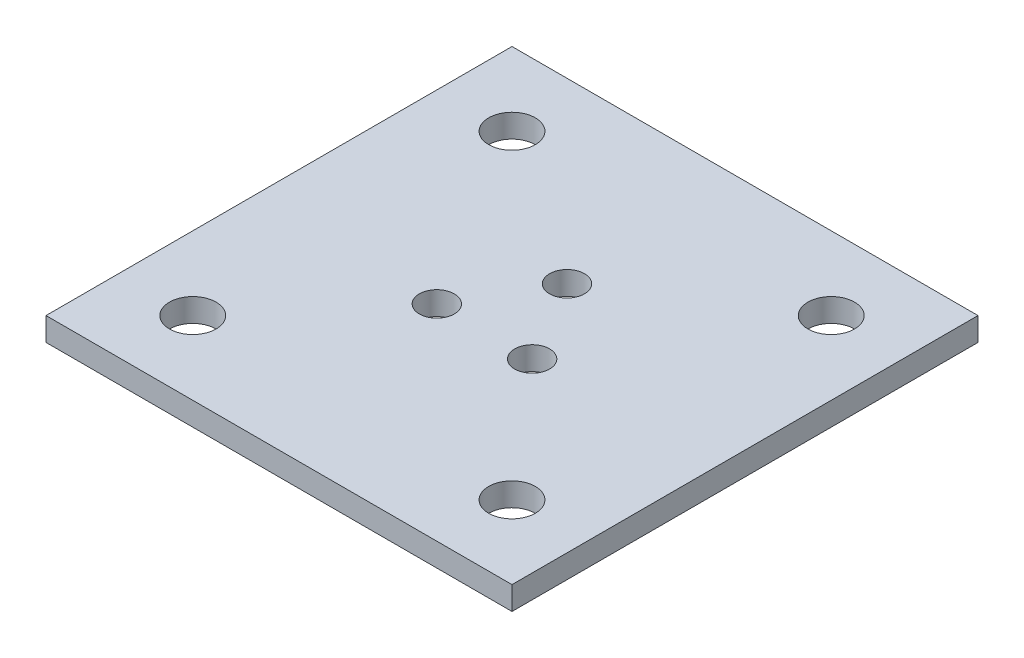
SolidWorks part; units mm, degrees
ref_plane "Front Plane" through (0, 0, 0) normal (0, 0, 1) x (1, 0, 0)
ref_plane "Top Plane" through (0, 0, 0) normal (0, 1, 0) x (1, 0, 0)
ref_plane "Right Plane" through (0, 0, 0) normal (1, 0, 0) x (0, 0, -1)
sketch "Sketch1" plane through (0, 0, 0) normal (0, 1, 0) x (1, 0, 0)
  line L1 (-31.75, -31.75) -> (31.75, -31.75)
  line L2 (-31.75, -31.75) -> (-31.75, 31.75)
  line L3 (-31.75, 31.75) -> (31.75, 31.75)
  line L4 (31.75, -31.75) -> (31.75, 31.75)
  line L5 (-31.75, -31.75) -> (31.75, 31.75) construction
  line L6 (-31.75, 31.75) -> (31.75, -31.75) construction
  circle A0 centre (0, 0) radius 19.05 construction
  dimension "D1" = 38.1
  dimension "D2" = 63.5
  dimension "D3" = 63.5
extrude "Boss-Extrude1" add sketch "Sketch1" along normal blind 3.175
sketch "Sketch2" plane through (0, 3.175, 0) normal (0, 1, 0) x (1, 0, 0)
  circle A0 centre (0, 0) radius 7.5 construction
  circle A1 centre (0, 7.5) radius 2.3812
  circle A2 centre (6.4952, -3.75) radius 2.3813
  circle A3 centre (-6.4952, -3.75) radius 2.3813
  point P11 (0, 0)
  dimension "D2" = 15
  dimension "D3" = 4.7625
  dimension "D1" = 3
extrude "Cut-Extrude1" cut sketch "Sketch2" against normal through all contours A1 | A3 | A2
sketch "Sketch3" plane through (0, 3.175, 0) normal (0, 1, 0) x (1, 0, 0)
  line L0 (-31.75, 31.75) -> (-31.75, -31.75) construction
  line L1 (-21.75, -21.75) -> (21.75, -21.75) construction
  line L2 (-21.75, -21.75) -> (-21.75, 21.75) construction
  line L3 (-21.75, 21.75) -> (21.75, 21.75) construction
  line L4 (21.75, -21.75) -> (21.75, 21.75) construction
  line L5 (-21.75, -21.75) -> (21.75, 21.75) construction
  line L6 (-21.75, 21.75) -> (21.75, -21.75) construction
  line L8 (-31.75, -31.75) -> (31.75, -31.75) construction
  circle A0 centre (-21.75, 21.75) radius 3.175
  circle A1 centre (21.75, 21.75) radius 3.175
  circle A2 centre (21.75, -21.75) radius 3.175
  circle A3 centre (-21.75, -21.75) radius 3.175
  point P0 (0, 0)
  dimension "D3" = 6.35
  dimension "D1" = 10
  dimension "D2" = 10
  dimension "D4" = 2
  dimension "D5" = 2
extrude "Cut-Extrude2" cut sketch "Sketch3" against normal through all contours A0 | A3 | A2 | A1 region at (-21.75, 3.175, -21.75) region at (21.75, 3.175, -21.75) region at (21.75, 3.175, 21.75) region at (-21.75, 3.175, 21.75)
